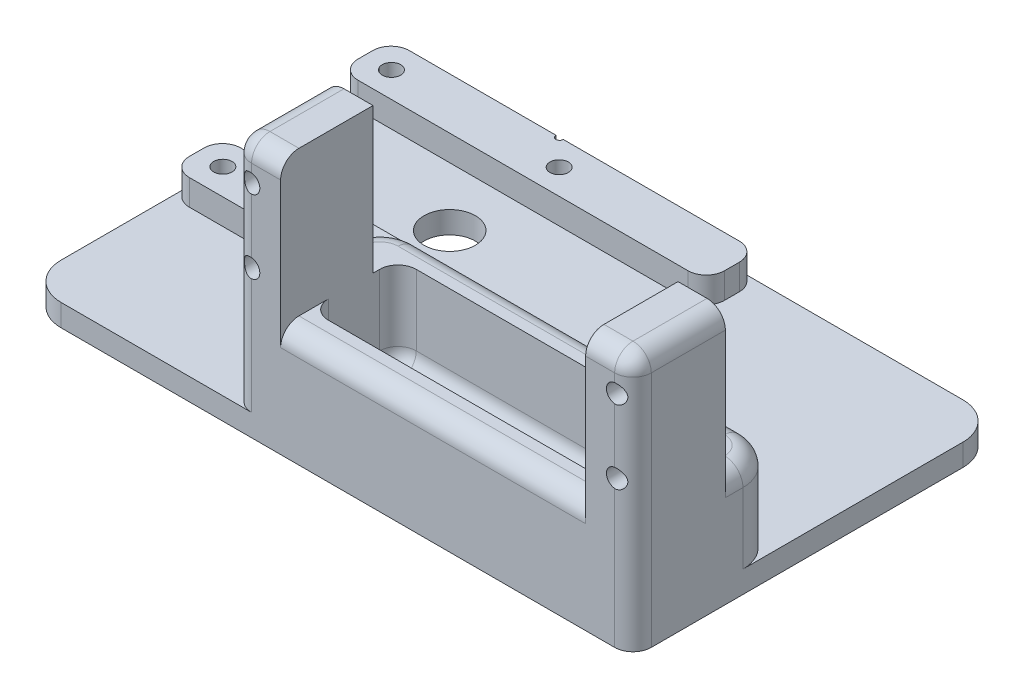
SolidWorks part; units mm, degrees
ref_plane "Front Plane" through (0, 0, 0) normal (0, 0, 1) x (1, 0, 0)
ref_plane "Top Plane" through (0, 0, 0) normal (0, 1, 0) x (1, 0, 0)
ref_plane "Right Plane" through (0, 0, 0) normal (1, 0, 0) x (0, 0, -1)
sketch "Sketch1" plane through (0, 0, 0) normal (0, 1, 0) x (1, 0, 0)
  line L1 (-41.5, 25) -> (41.5, 25)
  line L2 (-41.5, 25) -> (-41.5, -25)
  line L3 (-41.5, -25) -> (41.5, -25)
  line L4 (41.5, 25) -> (41.5, -25)
  line L5 (-41.5, 25) -> (41.5, -25) construction
  line L6 (-41.5, -25) -> (41.5, 25) construction
  point P0 (0, 0)
  dimension "D1" = 50
  dimension "D2" = 83
extrude "Boss-Extrude1" add sketch "Sketch1" along normal blind 3
sketch "Sketch2" plane through (0, 3, 0) normal (0, 1, 0) x (1, 0, 0)
  line L0 (-41.5, 25) -> (-41.5, -25) construction
  line L1 (-41.5, 25) -> (8.5, 25)
  line L2 (-41.5, 25) -> (-41.5, 18)
  line L3 (-41.5, 18) -> (8.5, 18)
  line L4 (8.5, 25) -> (8.5, 18)
  line L5 (-41.5, -5) -> (8.5, -5)
  line L6 (-41.5, -5) -> (-41.5, 2)
  line L7 (-41.5, 2) -> (8.5, 2)
  line L8 (8.5, -5) -> (8.5, 2)
  line L9 (-35.5574, 17.5) -> (6.6926, 17.5) construction
  line L10 (-35.5574, 2.5) -> (-1.632, 2.5) construction
  line L11 (-14, -5) -> (-39, -5) construction
  dimension "D1" = 0.5
  dimension "D2" = 0.5
  dimension "D3" = 50
extrude "Boss-Extrude2" add sketch "Sketch2" along normal up to surface (3.5 mm away)
sketch "Sketch3" plane through (0, 3, 0) normal (0, 1, 0) x (1, 0, 0)
  line L0 (40.5426, -12.4) -> (34.5426, -12.4) construction
  line L1 (41.5, -25) -> (35.0426, -25)
  line L2 (41.5, -25) -> (41.5, -12.4)
  line L3 (41.5, -12.4) -> (35.0426, -12.4)
  line L4 (35.0426, -25) -> (35.0426, -12.4)
  line L5 (-41.5, -25) -> (41.5, -25) construction
  line L6 (-13.0149, -25) -> (-6.5574, -25)
  line L7 (-13.0149, -25) -> (-13.0149, -12.4)
  line L8 (-13.0149, -12.4) -> (-6.5574, -12.4)
  line L9 (-6.5574, -25) -> (-6.5574, -12.4)
  line L10 (-12.0574, -12.4) -> (-6.0574, -12.4) construction
  line L11 (-6.0574, -32.9) -> (-6.0574, -12.4) construction
  line L12 (34.5426, -12.4) -> (34.5426, -32.9) construction
  dimension "D1" = 0.5
  dimension "D2" = 0.5
extrude "Boss-Extrude3" add sketch "Sketch3" along normal up to surface (31.93 mm away)
hole_wizard "M3x0.5 Tapped Hole1" positions "Sketch4" profile "Sketch5" tap size "M3x0.5" standard "ANSI Metric" end condition through all
sketch "Sketch4" plane through (0, 0, 12.4) normal (0, 0, -1) x (-1, 0, 0)
  point P0 (-39.1322, 30.03)
  point P3 (-39.1322, 20.03)
  point P6 (10.6471, 20.03)
  point P9 (10.6471, 30.03)
sketch "Sketch5" plane through (39.1322, 30.03, 12.4) normal (1, 0, 0) x (0, 1, 0)
  line L0 (0, 0) -> (0, 12.6)
  line L1 (0, 12.6) -> (1.25, 12.6)
  line L2 (1.25, 12.6) -> (1.25, 0)
  line L5 (1.25, 0) -> (0, 0)
  line L11 (0, -6.35) -> (0, 107.95) construction
  dimension "Thru Tap Drill Dia." = 2.5
  dimension "Thru Tap Drill Depth" = 12.6
cosmetic thread "Hole Thread1" parameters "D2"=3
cosmetic thread "Hole Thread2" parameters "D2"=3
cosmetic thread "Hole Thread3" parameters "D2"=3
cosmetic thread "Hole Thread4" parameters "D2"=3
sketch "Sketch6" plane through (0, 3, 0) normal (0, 1, 0) x (1, 0, 0)
  line L5 (41.5, -25) -> (-13.0149, -25)
  line L6 (41.5, -25) -> (41.5, -5)
  line L7 (41.5, -5) -> (-13.0149, -5)
  line L8 (-13.0149, -25) -> (-13.0149, -5)
  line L9 (-13.0149, -25) -> (-13.0149, -12.4) construction
  line L10 (-41.5, -5) -> (8.5, -5) construction
extrude "Boss-Extrude4" add sketch "Sketch6" along normal up to surface (12.13 mm away)
sketch "Sketch10" plane through (0, 15.13, 0) normal (0, 1, 0) x (1, 0, 0)
  line L0 (35.0426, -25) -> (35.0426, -12.4) construction
  line L1 (-6.5574, -21) -> (35.0426, -21)
  line L2 (-6.5574, -21) -> (-6.5574, -9)
  line L3 (-6.5574, -9) -> (35.0426, -9)
  line L4 (35.0426, -21) -> (35.0426, -9)
  line L5 (41.5, -5) -> (-13.0149, -5) construction
  line L7 (-6.5574, -12.4) -> (-6.5574, -25) construction
  line L8 (-6.5574, -25) -> (35.0426, -25) construction
  dimension "D1" = 4
  dimension "D2" = 4
extrude "Cut-Extrude2" cut sketch "Sketch10" against normal up to surface (12.13 mm away) up to face at (-27.2574, 3, 15)
fillet "Fillet1" radius 5 3 edges at (41.5, 9.065, 5) (8.5, 4.75, 5) (-13.0149, 4.75, 5)
fillet "Fillet2" radius 5 3 edges at (-13.0149, 10.815, 5) (-41.5, 1.5, 25) (41.5, 1.5, -25)
fillet "Fillet3" radius 2.5 7 edges at (8.5, 4.75, -18) (-41.5, 4.75, -18) (-41.5, 4.75, -2) (8.5, 4.75, -2) (8.5, 4.75, -25) (-41.5, 4.75, 5) (-41.5, 3.25, -25)
fillet "Fillet4" radius 2.5 6 edges at (41.5, 15.13, 11.2) (40.0355, 15.13, 6.4645) (-13.0149, 15.13, 11.2) (-11.5504, 15.13, 6.4645) (14.2426, 15.13, 25) (14.2426, 15.13, 5)
fillet "Fillet5" radius 2.5 6 edges at (41.5, 34.93, 18.7) (38.2713, 34.93, 25) (-9.7862, 34.93, 25) (-13.0149, 34.93, 18.7) (-13.0149, 18.965, 25) (41.5, 17.465, 25)
hole_wizard "M3x0.5 Tapped Hole2" positions "Sketch7" profile "Sketch8" tap size "M3x0.5" standard "ANSI Metric" end condition through all
sketch "Sketch7" plane through (0, 6.5, 0) normal (0, 1, 0) x (1, 0, 0)
  point P0 (-37.9955, -1.4337)
  point P3 (-15.0663, -1.4955)
  point P6 (-15.0045, 21.4337)
  point P9 (-37.9337, 21.4955)
sketch "Sketch8" plane through (-37.9955, 6.5, 1.4337) normal (1, 0, 0) x (0, 0, 1)
  line L0 (0, 0) -> (0, 6.5)
  line L1 (0, 6.5) -> (1.25, 6.5)
  line L2 (1.25, 6.5) -> (1.25, 0)
  line L5 (1.25, 0) -> (0, 0)
  line L11 (0, -6.35) -> (0, 107.95) construction
  dimension "Thru Tap Drill Dia." = 2.5
  dimension "Thru Tap Drill Depth" = 6.5
cosmetic thread "Hole Thread5" parameters "D2"=3
cosmetic thread "Hole Thread6" parameters "D2"=3
cosmetic thread "Hole Thread7" parameters "D2"=3
cosmetic thread "Hole Thread8" parameters "D2"=3
sketch "Sketch9" plane through (0, 3, 0) normal (0, 1, 0) x (1, 0, 0)
  line L0 (-26.5, 10) -> (-18.5, 10) construction
  circle A0 centre (-18.5, 10) radius 3.5
  dimension "D2" = 7
  dimension "D1" = 8
extrude "Cut-Extrude1" cut sketch "Sketch9" against normal through all
fillet "Fillet6" radius 2.5 8 edges at (-6.5574, 3, 15) (14.2426, 3, 21) (35.0426, 3, 15) (14.2426, 3, 9) (35.0426, 9.065, 21) (35.0426, 9.065, 9) (-6.5574, 9.065, 21) (-6.5574, 9.065, 9)
sketch "Sketch11" plane through (0, 0, 0) normal (0, -1, 0) x (1, 0, 0)
  line L0 (36.5, -25) -> (-39, -25) construction
  line L1 (-19, -25) -> (-18, -25)
  line L2 (-18.5, -10) -> (-18.5, -25) construction
  arc A0 (-19, -25) -> (-18, -25) centre (-18.5, -25) cw
  dimension "D1" = 0.5
extrude "Cut-Extrude3" cut sketch "Sketch11" against normal through all
